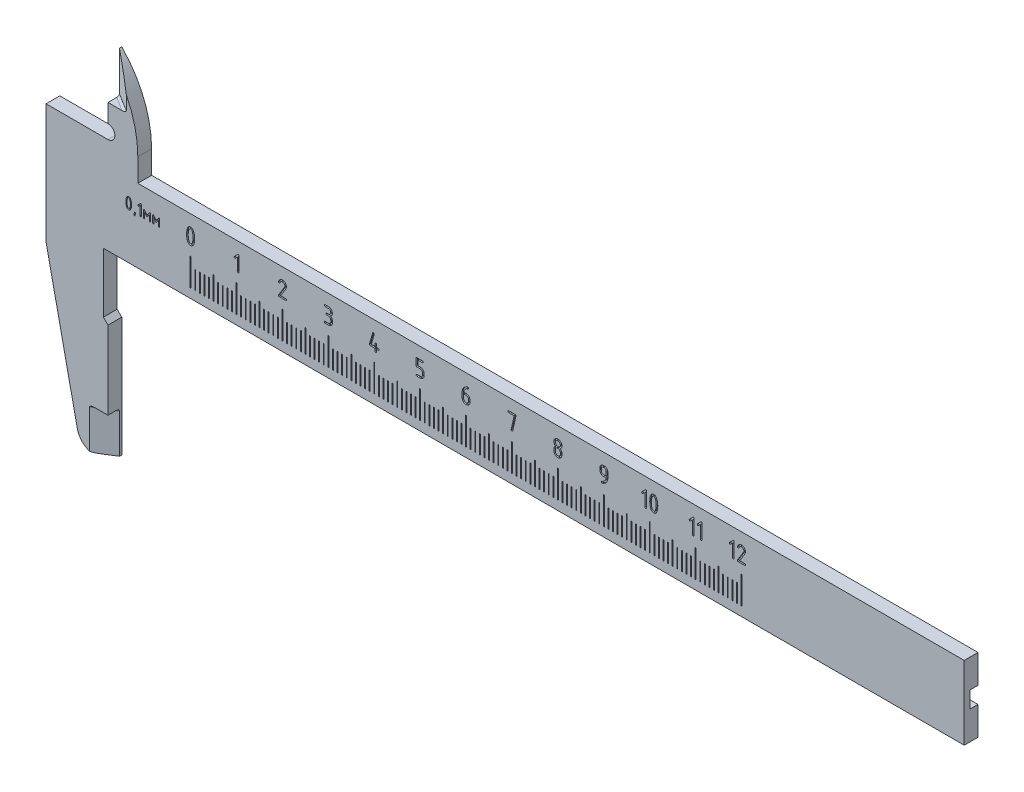
SolidWorks part; units mm, degrees
material "Простая углеродистая сталь"
ref_plane "Спереди" through (0, 0, 0) normal (0, 0, 1) x (1, 0, 0)
ref_plane "Сверху" through (0, 0, 0) normal (0, 1, 0) x (1, 0, 0)
ref_plane "Справа" through (0, 0, 0) normal (1, 0, 0) x (0, 0, -1)
sketch "Эскиз1" plane through (0, 0, 0) normal (0, 0, 1) x (1, 0, 0)
  line L0 (0, 13) -> (0, -13)
  line L1 (0, -13) -> (6.8225, -44.8381)
  line L2 (10.7337, -48) -> (13.5, -48)
  line L3 (13.5, -48) -> (13.5, -22)
  line L4 (13.5, -22) -> (12.5, -21)
  line L5 (12.5, -21) -> (12.5, -8)
  line L6 (12.5, -8) -> (200, -8)
  line L7 (200, -8) -> (200, 8)
  line L8 (200, 8) -> (20, 8)
  line L9 (20, 8) -> (20, 13)
  line L10 (0, 13) -> (13.5, 13)
  line L11 (13.5, 16) -> (13.5, 29)
  arc A0 (20, 13) -> (13.5, 29) centre (-2.9423, 13) ccw
  arc A1 (6.8225, -44.8381) -> (10.7337, -48) centre (10.7337, -44) ccw
  arc A2 (13.5, 13) -> (13.5, 16) centre (13.5, 14.5) ccw
  point P18 (7.5, -48)
  point P25 (200, 0)
  dimension "D7" = 4
  dimension "D12" = 1.5
  dimension "D2" = 1
  dimension "D3" = 45
  dimension "D4" = 13
  dimension "D5" = 61
  dimension "D6" = 6
  dimension "D8" = 26
  dimension "D9" = 21
  dimension "D10" = 16
  dimension "D11" = 6.5
  dimension "D13" = 16
  dimension "D14" = 200
  dimension "D15" = 12.095
extrude "Бобышка-Вытянуть1" add sketch "Эскиз1" along normal blind 3
sketch "Эскиз2" plane through (0, -48, 0) normal (0, -1, 0) x (1, 0, 0)
  line L0 (13.5, 3) -> (13.5, 0.5)
  line L1 (13.5, 3) -> (13.5, 0) construction
  line L2 (13.5, 0.5) -> (9.5, 3)
  line L3 (9.5, 3) -> (13.5, 3)
  line L4 (10.7337, 0) -> (13.5, 0) construction
  dimension "D1" = 0.5
  dimension "D2" = 4
extrude "Вырез-Вытянуть1" cut sketch "Эскиз2" against normal blind 9
ref_plane "Плоскость1" through (13.5, 29, 3) normal (0, -1, 0) x (-1, 0, 0)
sketch "Эскиз3" plane through (13.5, 29, 3) normal (0, -1, 0) x (-1, 0, 0)
  line L0 (0, 0) -> (0, 2.5)
  line L1 (0, 0) -> (0, 3) construction
  line L2 (0, 2.5) -> (-4, 0)
  line L3 (-4, 0) -> (0, 0)
  line L4 (0, 3) -> (-6.5, 3) construction
  dimension "D1" = 4
  dimension "D2" = 0.5
extrude "Вырез-Вытянуть2" cut sketch "Эскиз3" along normal blind 9
fillet "Скругление2" radius 0.5 2 edges at (15.5, 20, 1.75) (11.5, -39, 1.75)
sketch "Эскиз4" plane through (0, 0, 0) normal (0, 1, 0) x (1, 0, 0)
  line L0 (200, 0) -> (25, 0)
  line L1 (200, 0) -> (200, -1.75)
  line L2 (200, -1.75) -> (33.1815, -1.75)
  arc A0 (33.1815, -1.75) -> (25, 0) centre (33.1815, 18.25) cw
  dimension "D3" = 20
  dimension "D1" = 1.75
  dimension "D2" = 175
extrude "Вырез-Вытянуть3" cut sketch "Эскиз4" against normal mid plane 3.6
sketch "Эскиз5" plane through (0, -8, 0) normal (0, -1, 0) x (1, 0, 0)
  line L0 (31.4, 3) -> (31.5, 2.9)
  line L1 (12.5, 3) -> (200, 3) construction
  line L2 (31.5, 2.9) -> (31.6, 3)
  line L3 (31.6, 3) -> (31.4, 3)
  line L4 (12.5, 3) -> (12.5, 0) construction
  dimension "D1" = 0.2
  dimension "D2" = 19
extrude "Вырез-Вытянуть4" cut sketch "Эскиз5" against normal blind 6 from offset 2 offset against normal yes
pattern_linear "Линейный массив1" count 13 spacing 10 along (1, 0, 0) of "Вырез-Вытянуть4"
sketch "Эскиз6" plane through (0, -8, 0) normal (0, -1, 0) x (1, 0, 0)
  line L0 (32.4, 3) -> (32.5, 2.9)
  line L1 (12.5, 3) -> (200, 3) construction
  line L2 (32.5, 2.9) -> (32.6, 3)
  line L3 (32.6, 3) -> (32.4, 3)
  dimension "D1" = 0.2
  dimension "D2" = 1
extrude "Вырез-Вытянуть5" cut sketch "Эскиз6" against normal blind 4 from offset 2 offset against normal yes
pattern_linear "Линейный массив2" count 9 spacing 1 along (1, 0, 0) of "Вырез-Вытянуть5"
sketch "Эскиз7" plane through (0, -2, 0) normal (0, -1, 0) x (1, 0, 0)
  line L3 (36.6, 3) -> (36.4, 3)
  line L4 (36.4, 3) -> (36.5, 2.9)
  line L5 (36.5, 2.9) -> (36.6, 3)
  line L6 (36.6, 3) -> (36.4, 3)
  line L7 (36.4, 3) -> (36.5, 2.9)
  line L8 (36.5, 2.9) -> (36.6, 3)
  dimension "D1" = 0
extrude "Вырез-Вытянуть6" cut sketch "Эскиз7" against normal blind 1
pattern_linear "Линейный массив3" count 12 spacing 10 along (1, 0, 0) of "Вырез-Вытянуть6", "Линейный массив2"
sketch "Эскиз8" plane through (0, 0, 3) normal (0, 0, 1) x (1, 0, 0)
  line L0 (28.5, 2) -> (34.5, 2) construction
  line L1 (31.6, 0) -> (31.4, 0) construction
  line L2 (38.5, 2) -> (44.5, 2) construction
  line L3 (48.5, 2) -> (54.5, 2) construction
  line L4 (58.5, 2) -> (64.5, 2) construction
  line L5 (68.5, 2) -> (74.5, 2) construction
  line L6 (78.5, 2) -> (84.5, 2) construction
  line L7 (88.5, 2) -> (94.5, 2) construction
  line L8 (98.5, 2) -> (104.5, 2) construction
  line L9 (108.5, 2) -> (114.5, 2) construction
  line L10 (118.5, 2) -> (124.5, 2) construction
  line L11 (128.5, 2) -> (134.5, 2) construction
  line L12 (138.5, 2) -> (144.5, 2) construction
  line L13 (25, 2) -> (12.1555, 2) construction
  line L14 (20, 8) -> (20, 13) construction
  line L15 (148.5, 2) -> (154.5, 2) construction
  text T0 "0" font "ГОСТ тип А" height 3.5
  text T1 "1" font "ГОСТ тип А" height 3.5
  text T2 "2" font "ГОСТ тип А" height 3.5
  text T3 "3" font "ГОСТ тип А" height 3.5
  text T4 "4" font "ГОСТ тип А" height 3.5
  text T5 "5" font "ГОСТ тип А" height 3.5
  text T6 "6" font "ГОСТ тип А" height 3.5
  text T7 "7" font "ГОСТ тип А" height 3.5
  text T8 "8" font "ГОСТ тип А" height 3.5
  text T9 "9" font "ГОСТ тип А" height 3.5
  text T10 "10" font "ГОСТ тип А" height 3.5
  text T11 "11" font "ГОСТ тип А" height 3.5
  text T12 "0,1мм" font "ГОСТ тип А" height 2.5
  text T13 "12" font "ГОСТ тип А" height 3.5
  point P2 (31.5, 2)
  dimension "D1" = 2
  dimension "D2" = 6
  dimension "D4" = 10
  dimension "D5" = 5
  dimension "D3" = 13
extrude "Вырез-Вытянуть7" cut sketch "Эскиз8" against normal blind 0.3
